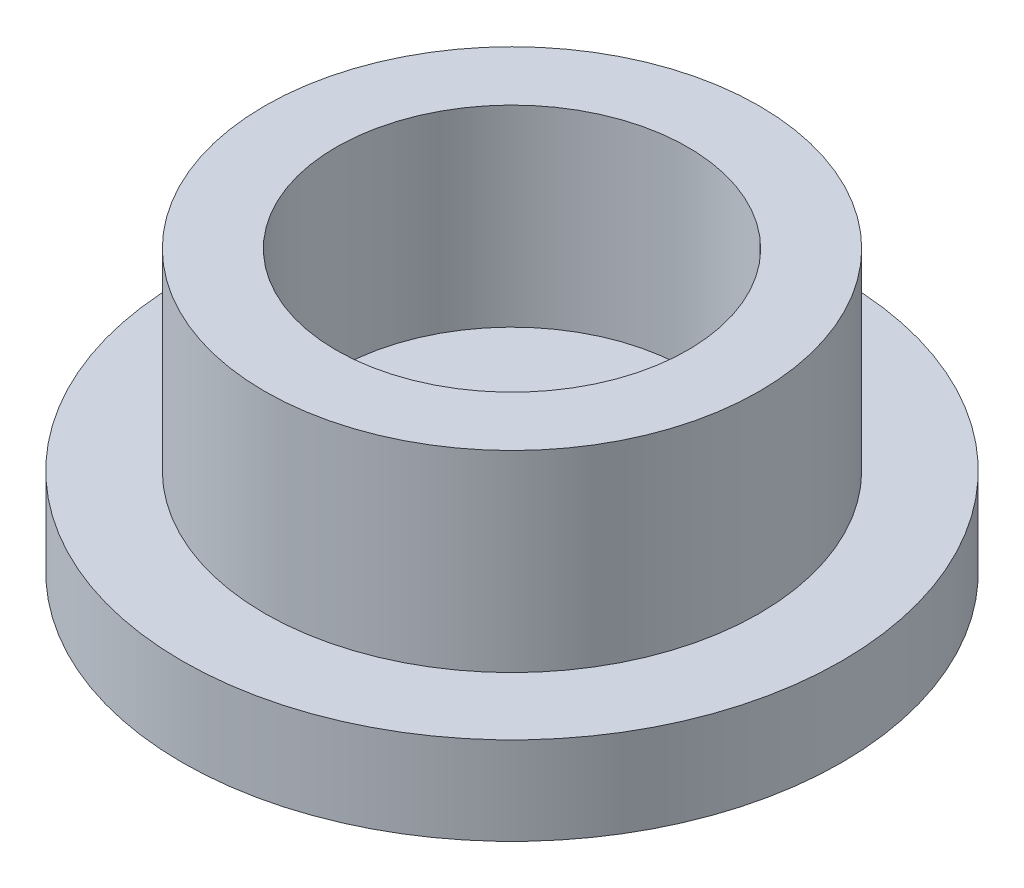
SolidWorks part; units mm, degrees
ref_plane "Front Plane" through (0, 0, 0) normal (0, 0, 1) x (1, 0, 0)
ref_plane "Top Plane" through (0, 0, 0) normal (0, 1, 0) x (1, 0, 0)
ref_plane "Right Plane" through (0, 0, 0) normal (1, 0, 0) x (0, 0, -1)
sketch "Sketch1" plane through (0, 0, 0) normal (0, 1, 0) x (1, 0, 0)
  circle A0 centre (0, 0) radius 1.6
  circle A1 centre (0, 0) radius 2.25
  dimension "D1" = 3.2
  dimension "D2" = 4.5
extrude "Boss-Extrude1" add sketch "Sketch1" along normal blind 1.75
sketch "Sketch2" plane through (0, 0, 0) normal (0, -1, 0) x (1, 0, 0)
  circle A0 centre (0, 0) radius 3
  dimension "D1" = 6
extrude "Boss-Extrude2" add sketch "Sketch2" along normal blind 0.8
